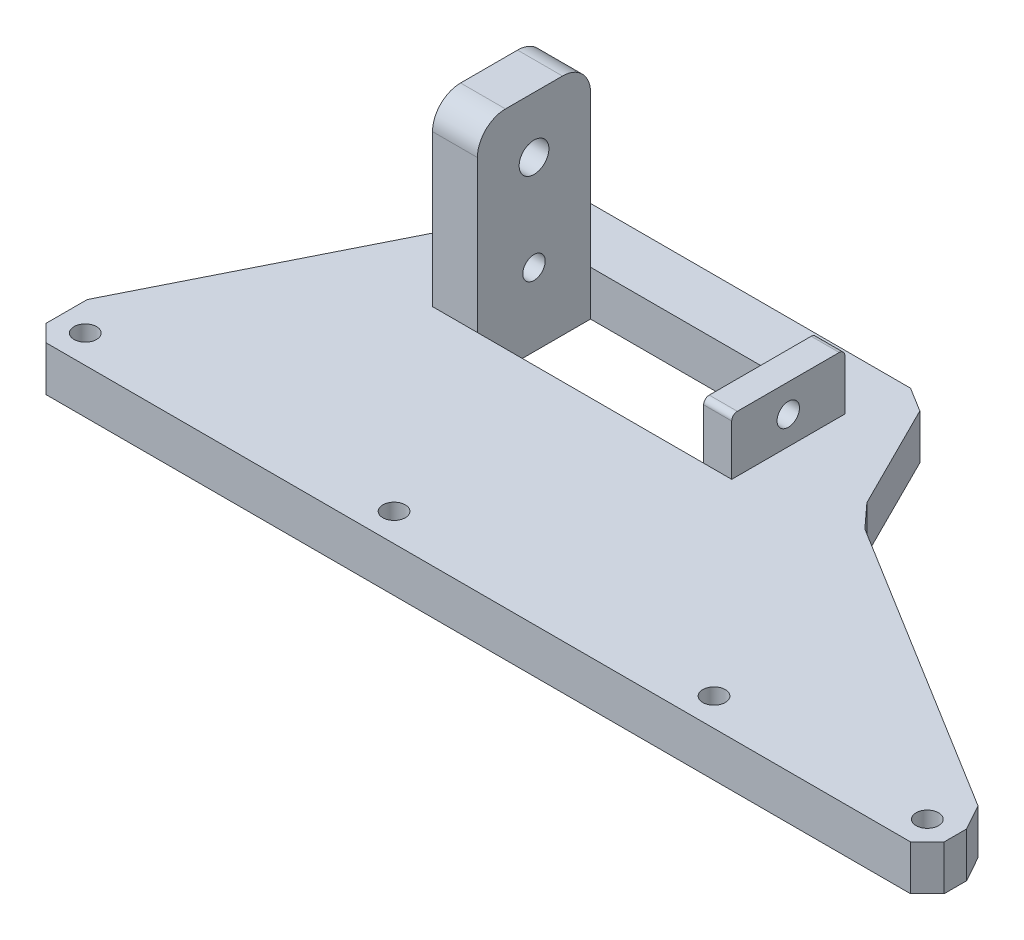
SolidWorks part; units mm, degrees
ref_plane "Alzado" through (0, 0, 0) normal (0, 0, 1) x (1, 0, 0)
ref_plane "Planta" through (0, 0, 0) normal (0, 1, 0) x (1, 0, 0)
ref_plane "Vista lateral" through (0, 0, 0) normal (1, 0, 0) x (0, 0, -1)
sketch "Croquis1" plane through (0, 0, 0) normal (0, 1, 0) x (1, 0, 0)
  line L1 (154, 0) -> (156.9981, 2.9981)
  line L2 (156.9981, 2.9981) -> (156.9981, 6.9981)
  line L3 (156.9981, 6.9981) -> (154.4465, 11.5749)
  line L4 (154.4465, 11.5749) -> (101.6651, 44.1989)
  line L5 (101.6651, 44.1989) -> (97.7729, 48.4584)
  line L6 (97.7729, 48.4584) -> (88.3473, 67.3137)
  line L7 (88.3473, 67.3137) -> (84.0091, 69.9952)
  line L8 (84.0091, 69.9952) -> (26.8414, 69.9952)
  line L9 (26.8414, 69.9952) -> (-2.9956, 10.3341)
  line L10 (-2.9956, 10.3341) -> (-2.9956, 3.0041)
  line L11 (-2.9956, 3.0041) -> (0, 0)
  line L13 (0, 0) -> (154, 0)
  line L14 (28.85, 60.15) -> (82.15, 60.15)
  line L15 (28.85, 40) -> (82.15, 40)
  line L16 (28.85, 40) -> (28.85, 60.15)
  line L18 (82.15, 40) -> (82.15, 60.15)
  line L19 (156.9981, 4.9981) -> (152, 4.9981) construction
  line L20 (152, 4.9981) -> (114, 4.9981) construction
  line L21 (114, 4.9981) -> (57, 4.9981) construction
  line L22 (57, 4.9981) -> (2, 4.9981) construction
  line L23 (28.85, 40) -> (28.85, 4.9981) construction
  line L24 (82.15, 60.15) -> (91.9284, 60.15) construction
  circle A0 centre (2, 4.9981) radius 2
  circle A1 centre (57, 4.9981) radius 2
  circle A2 centre (114, 4.9981) radius 2
  circle A3 centre (152, 4.9981) radius 2
  dimension "D1" = 135.081
  dimension "D2" = 2.9956
  dimension "D22" = 4
  dimension "D23" = 4
  dimension "D24" = 4
  dimension "D25" = 4
  dimension "D3" = 7.33
  dimension "D4" = 66.706
  dimension "D5" = 116.57
  dimension "D6" = 57.1677
  dimension "D7" = 4.3382
  dimension "D8" = 9.4256
  dimension "D9" = 195.86
  dimension "D10" = 195.86
  dimension "D11" = 3.8922
  dimension "D12" = 62.05
  dimension "D13" = 209.14
  dimension "D14" = 209.14
  dimension "D15" = 4
  dimension "D16" = 225
  dimension "D17" = 154
  dimension "D18" = 4.9981
  dimension "D19" = 38
  dimension "D20" = 57
  dimension "D21" = 55
  dimension "D26" = 26.85
  dimension "D27" = 35.0019
  dimension "D28" = 9.7784
  dimension "D29" = 53.3
extrude "Saliente-Extruir1" add sketch "Croquis1" along normal blind 8
sketch "Croquis2" plane through (0, 8, 0) normal (0, 1, 0) x (1, 0, 0)
  line L0 (28.85, 40) -> (82.15, 40) construction
  line L1 (28.85, 60.15) -> (36.85, 60.15)
  line L2 (28.85, 60.15) -> (28.85, 40)
  line L3 (28.85, 40) -> (36.85, 40)
  line L4 (36.85, 60.15) -> (36.85, 40)
  line L6 (82.15, 60.15) -> (77.15, 60.15)
  line L7 (82.15, 60.15) -> (82.15, 40)
  line L8 (82.15, 40) -> (77.15, 40)
  line L9 (77.15, 60.15) -> (77.15, 40)
  line M17 (28.85, 60.15) -> (82.15, 60.15)
  line M18 (82.15, 60.15) -> (82.15, 40)
  line M19 (82.15, 40) -> (28.85, 40)
  line M20 (28.85, 40) -> (28.85, 60.15)
  dimension "D1" = 8
  dimension "D2" = 5
extrude "Saliente-Extruir2" add sketch "Croquis2" against normal blind 8
extrude "Saliente-Extruir3" add sketch "Croquis2<4>" along normal blind 10 contours L9 M17 M19 M18 region at (79.65, 8, -50.075)
sketch "Croquis2<4>" plane through (0, 8, 0) normal (0, 1, 0) x (1, 0, 0) same geometry as "Croquis2"
extrude "Saliente-Extruir4" add sketch "Croquis2<5>" along normal blind 32 contours L4 M17 M20 M19 region at (32.85, 8, -50.075)
sketch "Croquis2<5>" plane through (0, 8, 0) normal (0, 1, 0) x (1, 0, 0) same geometry as "Croquis2"
sketch "Croquis4" plane through (77.15, 0, 0) normal (-1, 0, 0) x (0, 0, 1)
  line L0 (-50.075, 0) -> (-50.075, 13) construction
  line L1 (-60.15, 0) -> (-40, 0) construction
  circle A0 centre (-50.075, 13) radius 2
  dimension "D1" = 4
  dimension "D2" = 13
extrude "Cortar-Extruir1" cut sketch "Croquis4" against normal blind 32
extrude "Cortar-Extruir2" cut sketch "Croquis4<2>" along normal blind 74
sketch "Croquis4<2>" plane through (77.15, 0, 0) normal (-1, 0, 0) x (0, 0, 1) same geometry as "Croquis4"
sketch "Croquis5" plane through (36.85, 0, 0) normal (1, 0, 0) x (0, 0, -1)
  line L0 (50.08, 30) -> (50.08, 0) construction
  line L1 (48.4584, 0) -> (67.3137, 0) construction
  line L2 (0, 0) -> (50.08, 0) construction
  line L3 (11.5749, 0) -> (44.1989, 0) construction
  circle A0 centre (50.08, 30) radius 2.65
  dimension "D1" = 5.3
  dimension "D2" = 30
  dimension "D3" = 50.08
extrude "Cortar-Extruir3" cut sketch "Croquis5" against normal blind 35
sketch "Croquis6" plane through (82.15, 0, 0) normal (1, 0, 0) x (0, 0, -1)
  line L0 (40, 17) -> (40, 18)
  line L1 (40, 18) -> (41, 18)
  line L2 (59.15, 18) -> (60.15, 18)
  line L3 (60.15, 18) -> (60.15, 17)
  arc A0 (60.15, 17) -> (59.15, 18) centre (59.15, 17) ccw
  arc A1 (41, 18) -> (40, 17) centre (41, 17) ccw
  point P10 (60.15, 18)
  point P13 (40, 18)
  dimension "D1" = 1
  dimension "D2" = 1
  dimension "D3" = 1
  dimension "D4" = 1
extrude "Cortar-Extruir4" cut sketch "Croquis6" against normal blind 16
sketch "Croquis7" plane through (36.85, 0, 0) normal (1, 0, 0) x (0, 0, -1)
  line L0 (40, 35) -> (40, 40)
  line L3 (40, 40) -> (45, 40)
  line L5 (55.15, 40) -> (60.15, 40)
  line L6 (60.15, 40) -> (60.15, 35)
  arc A0 (60.15, 35) -> (55.15, 40) centre (55.15, 35) ccw
  arc A1 (45, 40) -> (40, 35) centre (45, 35) ccw
  point P12 (60.15, 40)
  point P15 (40, 40)
  dimension "D1" = 5
  dimension "D2" = 5
  dimension "D3" = 5
  dimension "D4" = 5
  dimension "D5" = 5
extrude "Cortar-Extruir5" cut sketch "Croquis7" against normal blind 16
